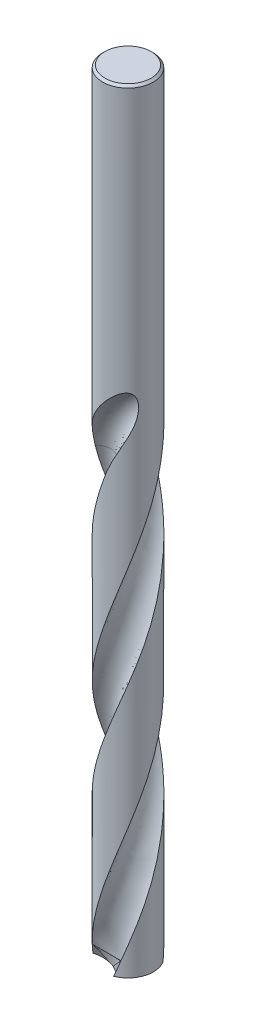
SolidWorks part; units mm, degrees
ref_plane "Front Plane" through (0, 0, 0) normal (0, 0, 1) x (1, 0, 0)
ref_plane "Top Plane" through (0, 0, 0) normal (0, 1, 0) x (1, 0, 0)
ref_plane "Right Plane" through (0, 0, 0) normal (1, 0, 0) x (0, 0, -1)
sketch "Sketch1" plane through (0, 0, 0) normal (0, 1, 0) x (1, 0, 0)
  circle A0 centre (0, 0) radius 2.25
  dimension "D1" = 4.5
extrude "Boss-Extrude1" add sketch "Sketch1" along normal blind 70
sketch "Sketch2" plane through (0, 0, 0) normal (0, -1, 0) x (1, 0, 0)
  circle A1 centre (0, 0) radius 2.25
  circle A2 centre (0, 0) radius 2.25
  dimension "D1" = 0
curve "Helix/Spiral1" pitch 40 height 40 turns 1
sketch3d "3DSketch1"
  arc A0 (1.125, 40, -1.9486) -> (-15.661, 48.1695, -0.3529) centre (-10.4829, 37.0112, 1.2439) ccw
  spline S0 degree 3 poles (-991.7307, -28.8315, -117.6778) (11.4826, -57.2604, 74.3294) (10.6788, -26.3625, -2.9697) (-0.5975, 4.9999, -2.2299) (-1.4054, 7.5, -1.8315) (-1.9993, 10, -1.1543) (-2.2888, 12.5, -0.3013) (-2.2299, 15, 0.5975) (-1.8315, 17.5, 1.4054) (-1.1543, 20, 1.9993) (-0.3013, 22.5, 2.2888) (0.5975, 25, 2.2299) (1.4054, 27.5, 1.8315) (1.9993, 30, 1.1543) (2.2888, 32.5, 0.3013) (2.2299, 35.0001, -0.5975) (-2.7676, 66.3624, -10.733) (-70.112, 97.2602, 27.2203) (597.7717, 68.8317, 800.0186) knots -2.165009 -2.165009 -2.165009 -2.165009 0.0625 0.125 0.1875 0.25 0.3125 0.375 0.4375 0.5 0.5625 0.625 0.6875 0.75 0.8125 0.875 0.9375 3.165002 3.165002 3.165002 3.165002 only from (1.125, 0, -1.9486) to (1.125, 40, -1.9486) construction
  spline S1 degree 3 poles (1.125, 0, -1.9486) (0.8701, 0.8327, -2.0957) (0.3013, 2.5003, -2.2889) (-0.5975, 4.9999, -2.2299) (-1.4054, 7.5, -1.8315) (-1.9993, 10, -1.1543) (-2.2888, 12.5, -0.3013) (-2.2299, 15, 0.5975) (-1.8315, 17.5, 1.4054) (-1.1543, 20, 1.9993) (-0.3013, 22.5, 2.2888) (0.5975, 25, 2.2299) (1.4054, 27.5, 1.8315) (1.9993, 30, 1.1543) (2.2888, 32.5, 0.3013) (2.2299, 35.0001, -0.5975) (1.8316, 37.4997, -1.4053) (1.3799, 39.1673, -1.8014) (1.125, 40, -1.9486) knots 0 0 0 0 0.0625 0.125 0.1875 0.25 0.3125 0.375 0.4375 0.5 0.5625 0.625 0.6875 0.75 0.8125 0.875 0.9375 1 1 1 1
  point P3 (-7.9709, 39.8666, 13.0509)
  point P5 (-15.6547, 48.8042, 0.5141)
sketch "Sketch3" plane through (0, 0, 0) normal (0, -1, 0) x (1, 0, 0)
  circle A0 centre (1.125, -1.9486) radius 1.5
  dimension "D1" = 3
sweep "Cut-Sweep1" cut profiles "Sketch3" path "3DSketch1"
pattern_circular "CirPattern1" count 2 over 360 about axis through (0, 70, 0) along (0, -1, 0) of "Cut-Sweep1"
sketch "Sketch4" plane through (0, 0, 0) normal (0, 0, 1) x (1, 0, 0)
  line L0 (0, -2.1216) -> (0, 2.4791) construction
  line L1 (0, 0) -> (-4.3599, 2.6197)
  line L2 (-4.3599, 2.6197) -> (-4.3599, -2.149)
  line L3 (-4.3599, -2.149) -> (0, -2.149)
  line L4 (0, 0) -> (0, -2.149)
  dimension "D1" = 59
revolve "Cut-Revolve1" cut sketch "Sketch4" angle 360 about L0
chamfer "Chamfer1" distance 0.2 angle 45 1 edges at (0, 70, 2.25)
